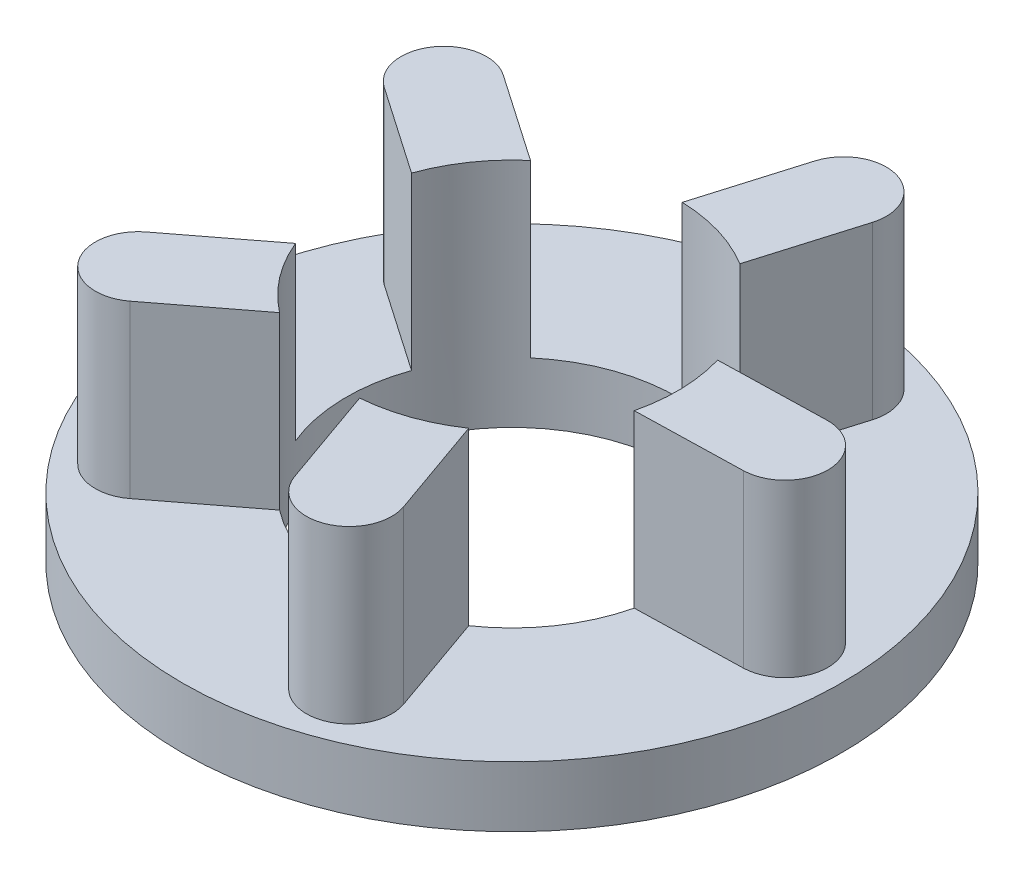
SolidWorks part; units mm, degrees
ref_plane "Front Plane" through (0, 0, 0) normal (0, 0, 1) x (1, 0, 0)
ref_plane "Top Plane" through (0, 0, 0) normal (0, 1, 0) x (1, 0, 0)
ref_plane "Right Plane" through (0, 0, 0) normal (1, 0, 0) x (0, 0, -1)
sketch "Sketch1" plane through (0, 0, 0) normal (0, 1, 0) x (1, 0, 0)
  line L0 (-6.8424, 3.2593) -> (-4.3799, 1.5618)
  line L1 (-2.6396, -8.8654) -> (7.6158, -5.25) construction
  line L2 (7.6158, -5.25) -> (7.3464, 5.6207) construction
  line L3 (7.3464, 5.6207) -> (-3.0754, 8.7238) construction
  line L4 (-3.0754, 8.7238) -> (-9.2472, -0.2291) construction
  line L5 (-9.2472, -0.2291) -> (-2.6396, -8.8654) construction
  line L6 (-5.4802, 5.2353) -> (-3.0177, 3.5378)
  line L7 (0.9854, 7.5147) -> (0.1319, 4.6481)
  line L8 (3.2856, 6.8298) -> (2.4321, 3.9633)
  line L9 (7.4514, 1.385) -> (4.4614, 1.3109)
  line L10 (7.5108, -1.0143) -> (4.5208, -1.0884)
  line L11 (3.6198, -6.6587) -> (2.6254, -3.8379)
  line L12 (1.3563, -7.4567) -> (0.3619, -4.6359)
  line L13 (-5.2142, -5.5003) -> (-2.8388, -3.6829)
  line L14 (-6.6726, -3.5942) -> (-4.2972, -1.7768)
  circle A0 centre (0, 0) radius 9.25
  circle A2 centre (0, 0) radius 4.65
  circle A3 centre (0, 0) radius 7.4834 construction
  arc A4 (-5.4032, 5.1775) -> (-6.761, 3.2079) centre (-6.1613, 4.2473) ccw
  arc A5 (3.2544, 6.7387) -> (0.9616, 7.4214) centre (2.1355, 7.1722) ccw
  arc A6 (7.4146, -1.0128) -> (7.3553, 1.3787) centre (7.4811, 0.1854) ccw
  arc A7 (1.328, -7.3646) -> (3.5842, -6.5693) centre (2.4881, -7.0577) ccw
  arc A8 (-6.5938, -3.5388) -> (-5.1402, -5.4388) centre (-5.9434, -4.5472) ccw
  dimension "D1" = 18.5
  dimension "D2" = 2.4
  dimension "D3" = 9.3
  dimension "D4" = 2.4
  dimension "D5" = 2.4
  dimension "D6" = 2.4
  dimension "D7" = 2.4
extrude "Boss-Extrude1" add sketch "Sketch1" along normal blind 4.8 contours L14 A8 L13 A2 | L6 A4 L0 A2 | L8 A5 L7 A2 | L10 A6 L9 A2 | L12 A7 L11 A2 region at (-5.3689, 0, -3.7011) region at (-5.179, 0, 3.9624) region at (1.8609, 0, -6.2498) region at (2.1681, 0, 6.15) region at (6.519, 0, -0.1615)
extrude "Boss-Extrude2" add sketch "Sketch1<3>" against normal blind 1.7 contours L8 A5 L7 A2 | L10 A6 L9 A2 | L12 A7 L11 A2 | L14 A8 L13 A2 | L6 A4 L0 A2 | A0 A8 L14 A2 L0 A4 L6 L7 A5 L8 L9 A6 L10 L11 A7 L12 L13 region at (-5.3689, 0, -3.7011) region at (-5.179, 0, 3.9624) region at (1.8609, 0, -6.2498) region at (2.1681, 0, 6.15) region at (6.519, 0, -0.1615) region at (-8.9884, 0, 0)
sketch "Sketch1<3>" plane through (0, 0, 0) normal (0, 1, 0) x (1, 0, 0) same geometry as "Sketch1"
